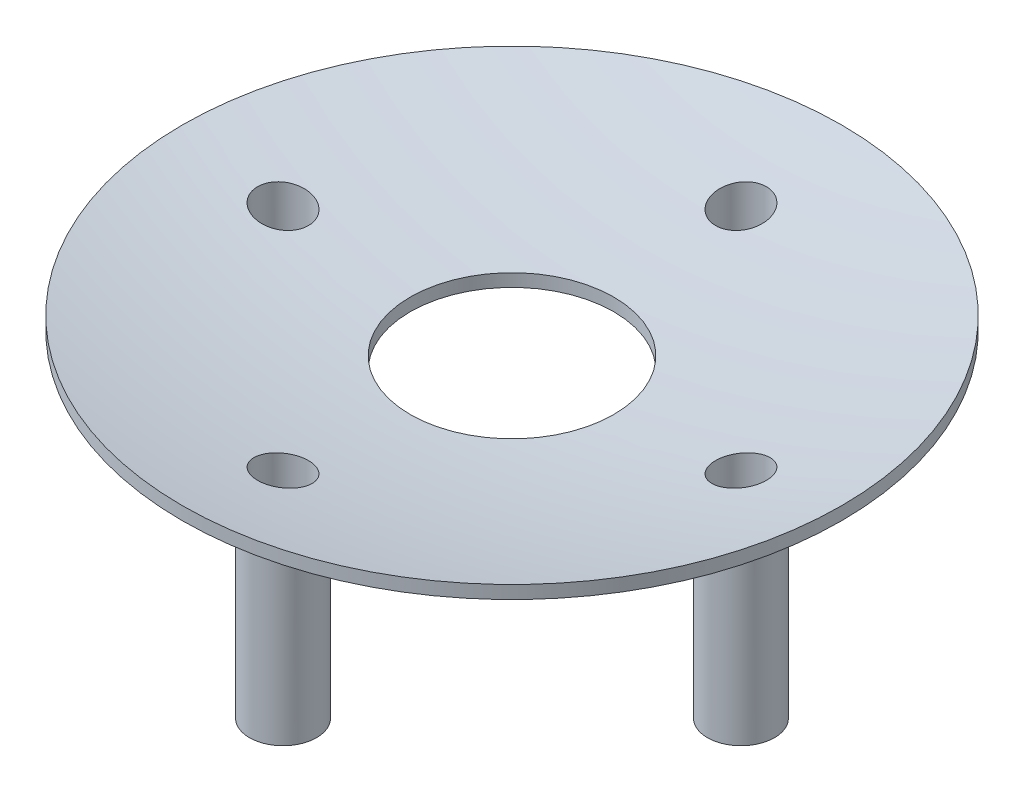
SolidWorks part; units mm, degrees
ref_plane "Front Plane" through (0, 0, 0) normal (0, 0, 1) x (1, 0, 0)
ref_plane "Top Plane" through (0, 0, 0) normal (0, 1, 0) x (1, 0, 0)
ref_plane "Right Plane" through (0, 0, 0) normal (1, 0, 0) x (0, 0, -1)
sketch "Sketch1" plane through (0, 0, 0) normal (0, 0, 1) x (1, 0, 0)
  line L0 (0, 1.5875) -> (0, 0)
  line L1 (0, 0) -> (0, 179.3875) construction
  line L2 (-71.1386, 16.4392) -> (-72.5877, 15.3421)
  arc A0 (0, 1.5875) -> (-71.1386, 16.4392) centre (0, 179.3875) cw
  arc A1 (0, 0) -> (-72.5877, 15.3421) centre (0, 179.3875) cw
revolve "Revolve1" add sketch "Sketch1" angle 360 about L1
sketch "Sketch2" plane through (0, 0, 0) normal (0, 1, 0) x (1, 0, 0)
  circle A0 centre (0, 0) radius 41.148
  circle A1 centre (0, -28.575) radius 3.175
  circle A2 centre (28.575, 0) radius 3.175
  circle A3 centre (0, 28.575) radius 3.175
  circle A4 centre (-28.575, 0) radius 3.175
  circle A5 centre (0, -28.575) radius 4.191
  circle A6 centre (28.575, 0) radius 4.191
  circle A7 centre (0, 28.575) radius 4.191
  circle A8 centre (-28.575, 0) radius 4.191
  circle A9 centre (0, 0) radius 12.7
  circle A10 centre (0, 0) radius 72.5877
extrude "Boss-Extrude2" add sketch "Sketch2" along normal up to surface and the other way blind 22.86 contours A8 A4 | A4 | A3 | A7 A3 | A2 | A6 A2 | A1 | A5 A1 region at (0, 0, 28.575) region at (28.575, 0, 0) region at (0, 0, -28.575) region at (-28.575, 0, 0) region at (-4.0725, 0, 28.575) region at (24.5025, 0, 0) region at (-4.0725, 0, -28.575) region at (-32.6475, 0, 0) up to face at (0, 15.3421, -72.5877)
extrude "Cut-Extrude3" cut sketch "Sketch2<6>" along normal through all contours A10 A0 | A9 region at (0, 0, 0) region at (-70.5346, 0, 0) body kept at (41.148, 6.4144, 0)
sketch "Sketch2<6>" plane through (0, 0, 0) normal (0, 1, 0) x (1, 0, 0) same geometry as "Sketch2"
extrude "Cut-Extrude4" cut sketch "Sketch2<8>" against normal through all and the other way through all contours A4 | A3 | A2 | A1 region at (0, 0, 28.575) region at (28.575, 0, 0) region at (0, 0, -28.575) region at (-28.575, 0, 0)
sketch "Sketch2<8>" plane through (0, 0, 0) normal (0, 1, 0) x (1, 0, 0) same geometry as "Sketch2"
